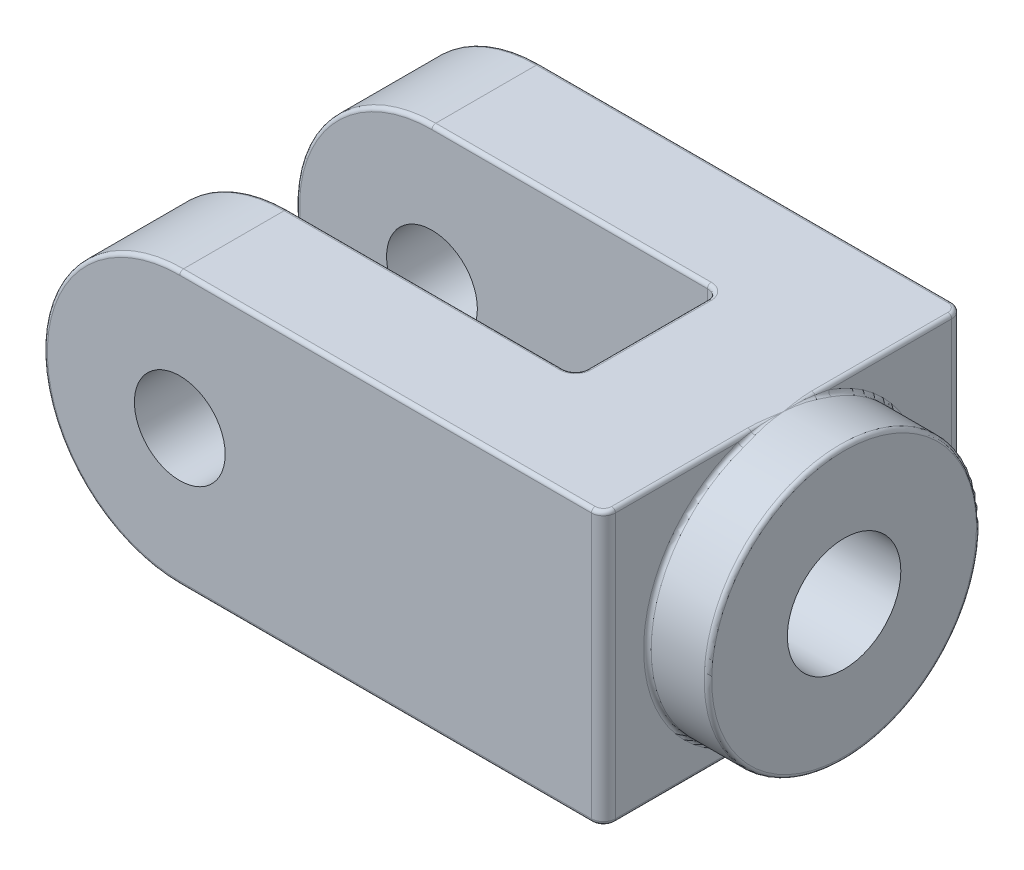
SolidWorks part; units mm, degrees
ref_plane "Front Plane" through (0, 0, 0) normal (0, 0, 1) x (1, 0, 0)
ref_plane "Top Plane" through (0, 0, 0) normal (0, 1, 0) x (1, 0, 0)
ref_plane "Right Plane" through (0, 0, 0) normal (1, 0, 0) x (0, 0, -1)
sketch "Sketch1" plane through (0, 0, 0) normal (0, 0, 1) x (1, 0, 0)
  line L0 (0, 0) -> (0, -47671.9315) construction
  line L1 (0, 0) -> (47671.9315, 0) construction
  line L2 (0, 36) -> (0, -36)
  line L3 (0, -36) -> (-112, -36)
  line L4 (-112, 36) -> (0, 36)
  line L5 (-36, 36) -> (-36, -36)
  arc A0 (-112, -36) -> (-112, 36) centre (-112, 0) cw
  circle A1 centre (-112, 0) radius 12
  point P8 (0, 0)
  dimension "D3" = 24
  dimension "D1" = 112
  dimension "D2" = 72
  dimension "D4" = 36
extrude "Boss-Extrude1" add sketch "Sketch1" along normal mid plane 95.25 contours L4 L5 L3 L2 region at (-18, 0, 0)
extrude "Boss-Extrude2" add sketch "Sketch1<3>" along normal blind 28.575 from offset 19.05 contours A0 L3 L5 L4 A1 region at (-86.9365, 0, 0)
sketch "Sketch1<3>" plane through (0, 0, 0) normal (0, 0, 1) x (1, 0, 0) same geometry as "Sketch1"
mirror "Mirror1" about plane through (0, 0, 0) normal (0, 0, 1) of "Boss-Extrude2"
sketch "Sketch2" plane through (0, 0, 0) normal (1, 0, 0) x (0, 0, -1)
  line L0 (-47.625, 36) -> (47.625, 36) construction
  circle A0 centre (0, 0) radius 36
extrude "Boss-Extrude3" add sketch "Sketch2" along normal blind 16
hole_wizard "Ø1.0mm Dowel Hole1" positions "Sketch3" profile "Sketch4" hole size "Ø1.0" standard "ANSI Metric" end condition up to next
sketch "Sketch3" plane through (16, 0, 0) normal (1, 0, 0) x (0, 0, -1)
  point P0 (0, 0)
sketch "Sketch4" plane through (16, 0, 0) normal (0, 1, 0) x (0, 0, -1)
  line L0 (0, 0) -> (0, 52)
  line L1 (0, 52) -> (15, 52)
  line L2 (15, 52) -> (15, 0)
  line L5 (15, 0) -> (0, 0)
  line L11 (0, -6.35) -> (0, 107.95) construction
  dimension "Thru Hole Dia." = 30
  dimension "Thru Hole Depth" = 52
fillet "Fillet1" radius 3.175 4 edges at (-36, 0, -19.05) (-36, 0, 19.05) (0, 0, 47.625) (0, 0, -47.625)
fillet "Fillet2" radius 1 26 edges at (-0.9299, -36, 46.6951) (0, -36, 22.225) (0, -36, -22.225) (-0.9299, -36, -46.6951) (-57.5875, -36, -47.625) (-148, 0, -47.625) (-57.5875, 36, -47.625) (-0.9299, 36, -46.6951) (0, 36, -22.225) (0, 36, 22.225) (-0.9299, 36, 46.6951) (-57.5875, 36, 47.625) (-148, 0, 47.625) (-57.5875, -36, 47.625) (-36.9299, -36, 18.1201) (-36, -36, 0) (-36.9299, -36, -18.1201) (-75.5875, -36, -19.05) (-148, 0, -19.05) (-75.5875, 36, -19.05) (-36.9299, 36, -18.1201) (-36, 36, 0) (-36.9299, 36, 18.1201) (-75.5875, 36, 19.05) (-148, 0, 19.05) (-75.5875, -36, 19.05)
fillet "Fillet3" radius 1 7 edges at (0, 35.7491, -4.2426) (0, 0, -36) (0, -35.7491, -4.2426) (0, -35.7491, 4.2426) (0, 0, 36) (0, 35.7491, 4.2426) (16, 36, 0)
